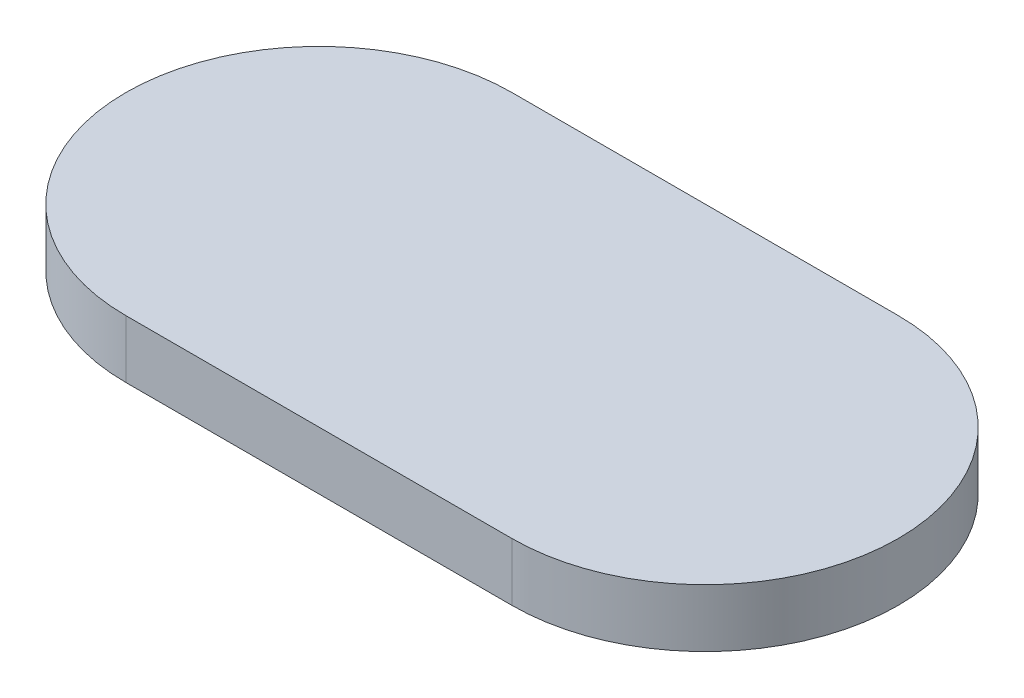
SolidWorks part; units mm, degrees
ref_plane "Front Plane" through (0, 0, 0) normal (0, 0, 1) x (1, 0, 0)
ref_plane "Top Plane" through (0, 0, 0) normal (0, 1, 0) x (1, 0, 0)
ref_plane "Right Plane" through (0, 0, 0) normal (1, 0, 0) x (0, 0, -1)
sketch "Sketch2" plane through (0, 0, 0) normal (0, 1, 0) x (1, 0, 0)
  line L0 (15, 0) -> (-15, 0) construction
  line L1 (15, 15) -> (-15, 15)
  line L2 (15, -15) -> (-15, -15)
  arc A0 (15, 15) -> (15, -15) centre (15, 0) cw
  arc A1 (-15, 15) -> (-15, -15) centre (-15, 0) ccw
  point P4 (0, 0)
  dimension "D1" = 30
  dimension "D2" = 15
  dimension "D3" = 15
extrude "Boss-Extrude1" add sketch "Sketch2" along normal blind 4.5
